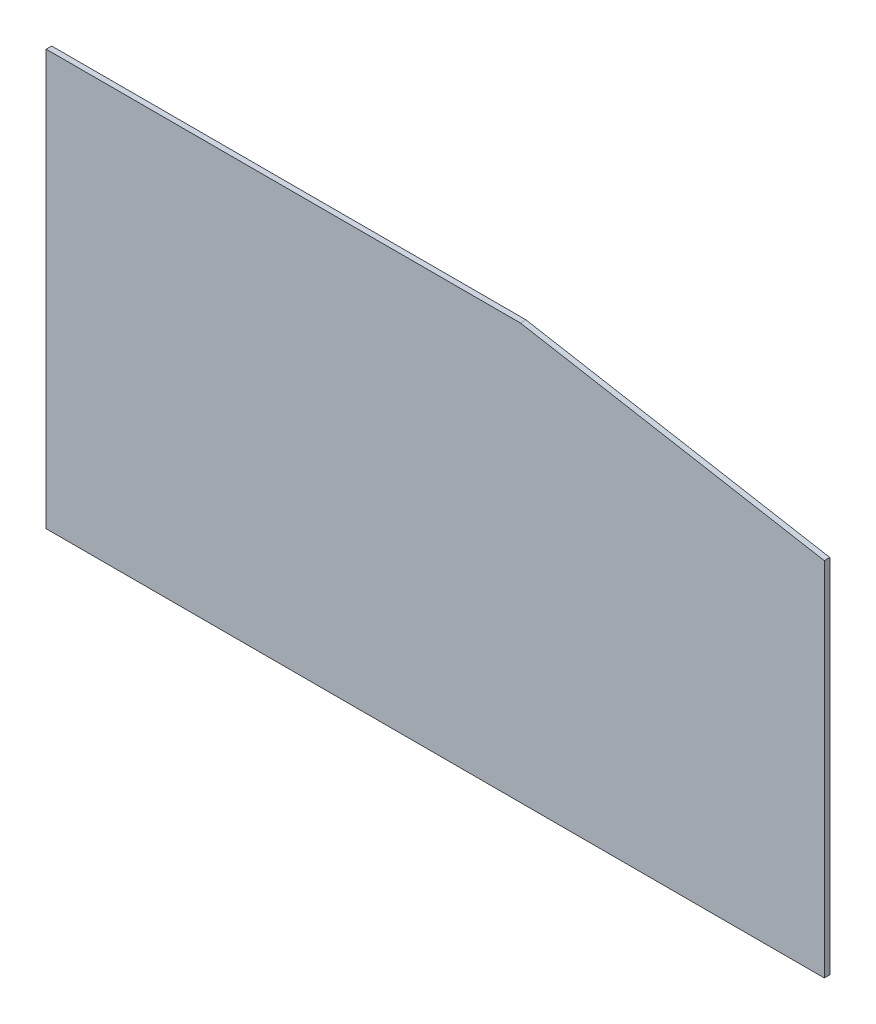
SolidWorks part; units mm, degrees
ref_plane "Ön Düzlem" through (0, 0, 0) normal (0, 0, 1) x (1, 0, 0)
ref_plane "Üst Düzlem" through (0, 0, 0) normal (0, 1, 0) x (1, 0, 0)
ref_plane "Sağ Düzlem" through (0, 0, 0) normal (1, 0, 0) x (0, 0, -1)
sketch "Çizim1" plane through (0, 0, 0) normal (0, 0, 1) x (1, 0, 0)
  line L0 (0, 0) -> (0, 795)
  line L1 (0, 795) -> (660, 912)
  line L2 (660, 912) -> (1840, 912)
  line L3 (1840, 912) -> (2500, 795)
  line L4 (2500, 795) -> (2500, 0)
  line L5 (2500, 0) -> (0, 0)
  line L6 (640, 908.4545) -> (640, 0) construction
  dimension "D1" = 795
  dimension "D2" = 912
  dimension "D3" = 660
  dimension "D4" = 660
  dimension "D5" = 2500
  dimension "D6" = 640
  dimension "D7" = 908.4545
  dimension "D8" = 113.4545
  dimension "D9" = 640
base flange "Taban-Flanş1" sketch "Çizim1" thickness 12 reverse thickness direction no parameters "D1"=8
sketch "Çizim2" plane through (0, 0, 0) normal (0, 0, 1) x (1, 0, 0)
  line L0 (2500, 0) -> (2500, 795) construction
  line L1 (0, 0) -> (2500, 0)
  line L2 (0, 0) -> (0, 10)
  line L3 (0, 10) -> (2500, 10)
  line L4 (2500, 0) -> (2500, 10)
  dimension "D1" = 785
extrude "Kes-Ekstrüzyon1" cut sketch "Çizim2" against normal through all both and the other way through all
sketch "Çizim3" plane through (0, 0, 0) normal (0, 0, 1) x (1, 0, 0)
  line L0 (1840, 912) -> (660, 912) construction
  line L1 (2500, 10) -> (810, 10) construction
  line L2 (2500, 10) -> (2500, 912) construction
  line L3 (2500, 912) -> (810, 912) construction
  line L4 (810, 10) -> (810, 912)
  line L5 (0, 795) -> (0, 10) construction
  line L7 (810, 912) -> (-172.47, 1159.1596)
  line L8 (-172.47, 1159.1596) -> (-279.2706, -118.4922)
  line L9 (-279.2706, -118.4922) -> (448.5558, -150.1369)
  line L10 (448.5558, -150.1369) -> (810, 10)
  dimension "D1" = 810
  dimension "D2" = 902
  dimension "D3" = 1690
extrude "Kes-Ekstrüzyon2" cut sketch "Çizim3" against normal through all both and the other way through all
sketch "Büküm-Çizgileri1" [suppressed] plane through (0, 0, 0) normal (0, 1, 0) x (1, 0, 0)
sketch "Sınırlandırma-Kutusu1" [suppressed] plane through (0, 0, 0) normal (0, 1, 0) x (1, 0, 0)
sheet metal parameters "Sac-Levha1" thickness 12 parameters "D1"=8
flat pattern "Düz-Çoğaltma1" [suppressed]
sketch "Büküm-Çizgileri2" plane through (0, 0, 0) normal (0, 1, 0) x (1, 0, 0)
sketch3d "Sınırlandırma-Kutusu2" [suppressed]
  line L0 (0, 0, 0) -> (-2500, 0, 0) construction
  line L1 (0, 912, 0) -> (-2500, 912, 0) construction
  line L2 (0, 0, 0) -> (0, 912, 0) construction
  line L3 (-2500, 0, 0) -> (-2500, 912, 0) construction
sheet metal parameters "Sac-Levha2" thickness 12 parameters "D1"=8
flat pattern "Düz-Çoğaltma1"
sketch "Büküm-Çizgileri2" plane through (0, 0, 0) normal (0, 1, 0) x (1, 0, 0)
sketch3d "Sınırlandırma-Kutusu2" [suppressed]
  line L0 (0, 10, 0) -> (2500, 10, 0) construction
  line L1 (0, 912, 0) -> (2500, 912, 0) construction
  line L2 (0, 10, 0) -> (0, 912, 0) construction
  line L3 (2500, 10, 0) -> (2500, 912, 0) construction
sheet metal parameters "Sac-Levha3" thickness 12 parameters "D1"=8
flat pattern "Düz-Çoğaltma1"
sketch "Büküm-Çizgileri2" plane through (0, 0, 0) normal (0, 1, 0) x (1, 0, 0)
sketch3d "Sınırlandırma-Kutusu2" [suppressed]
  line L0 (810, 10, 0) -> (2500, 10, 0) construction
  line L1 (810, 912, 0) -> (2500, 912, 0) construction
  line L2 (810, 10, 0) -> (810, 912, 0) construction
  line L3 (2500, 10, 0) -> (2500, 912, 0) construction
